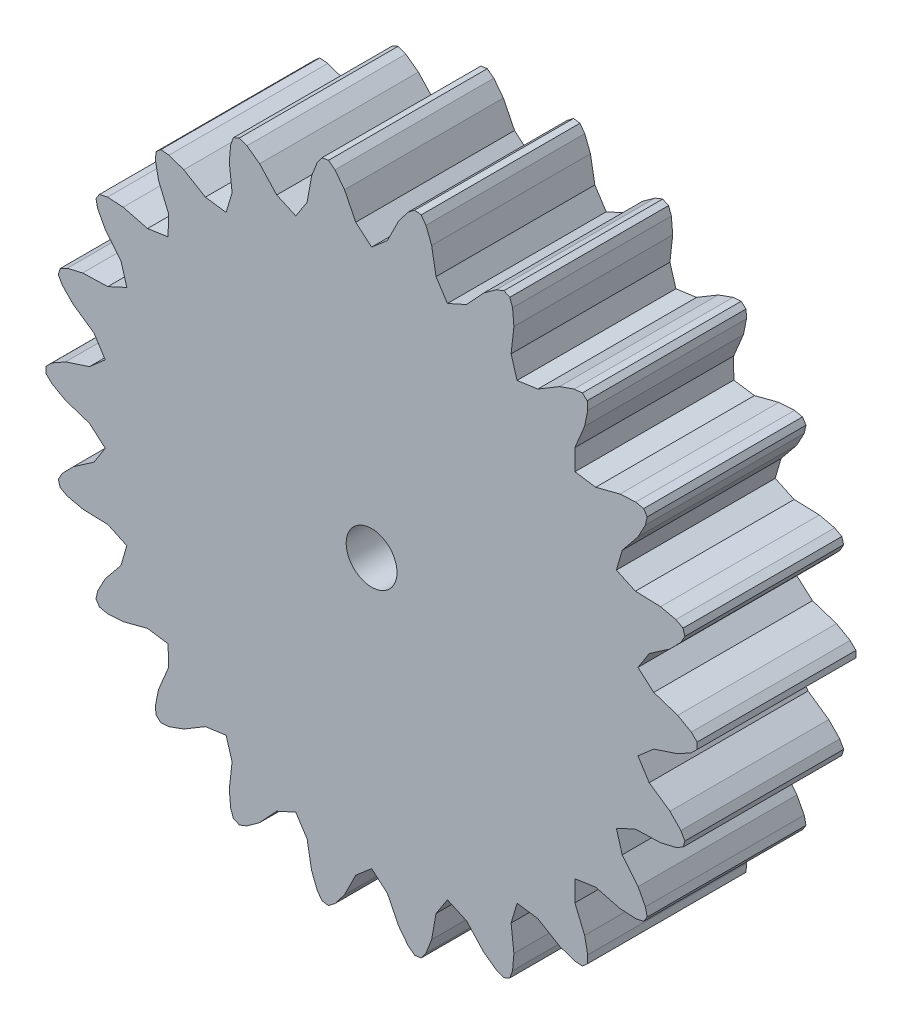
SolidWorks part; units mm, degrees
ref_plane "Front Plane" through (0, 0, 0) normal (0, 0, 1) x (1, 0, 0)
ref_plane "Top Plane" through (0, 0, 0) normal (0, 1, 0) x (1, 0, 0)
ref_plane "Right Plane" through (0, 0, 0) normal (1, 0, 0) x (0, 0, -1)
sketch "Sketch1" plane through (0, 0, 0) normal (0, 0, 1) x (1, 0, 0)
  line L1 (1.2374, -1.2374) -> (-1.2374, -1.2374) construction
  line L2 (1.2374, -1.2374) -> (1.2374, 1.2374) construction
  line L3 (1.2374, 1.2374) -> (-1.2374, 1.2374) construction
  line L4 (-1.2374, -1.2374) -> (-1.2374, 1.2374) construction
  line L5 (1.2374, -1.2374) -> (-1.2374, 1.2374) construction
  line L6 (1.2374, 1.2374) -> (-1.2374, -1.2374) construction
  circle A0 centre (0, 0) radius 20.5
  circle A1 centre (0, 0) radius 1.75 construction
  dimension "D1" = 41
  dimension "D2" = 3.5
extrude "Boss-Extrude1" add sketch "Sketch1" along normal blind 10
sketch "Sketch2" plane through (0, 0, 0) normal (0, 0, 1) x (1, 0, 0)
  line L0 (0, 0) -> (0, 10.088) construction
  line L1 (0, 16.9447) -> (-0.9985, 17.8041)
  line L8 (-2.7154, 20.3194) -> (0, 24.5037)
  line L11 (-0.9985, 17.8041) -> (-1.7043, 19.2252)
  line L12 (-1.7043, 19.2252) -> (-2.3066, 20.0063)
  line L13 (-2.3066, 20.0063) -> (-2.7154, 20.3194)
  line L14 (2.3066, 20.0063) -> (2.7154, 20.3194)
  line L15 (1.7043, 19.2252) -> (2.3066, 20.0063)
  line L16 (0.9985, 17.8041) -> (1.7043, 19.2252)
  line L17 (2.7154, 20.3194) -> (0, 24.5037)
  line L18 (0, 16.9447) -> (0.9985, 17.8041)
  circle A14 centre (0, 0) radius 20.5 construction
  point P16 (0, 20.5)
extrude "Cut-Extrude1" cut sketch "Sketch2" along normal through all
sketch "Sketch3" plane through (0, 0, 0) normal (0, 0, 1) x (1, 0, 0)
  circle A0 centre (0, 0) radius 7.5
  dimension "D1" = 15
sketch "Sketch4" plane through (0, 0, 10) normal (0, 0, 1) x (1, 0, 0)
  circle A0 centre (0, 0) radius 1.6
  dimension "D1" = 3.2
extrude "Cut-Extrude2" cut sketch "Sketch4" against normal through all both and the other way through all
pattern_circular "CirPattern1" count 22 over 360 about axis through (0, 0, 10) along (0, 0, -1) of "Cut-Extrude1" reverse direction yes
equation "\"circle\"=41"
equation "\"D1@Sketch1\"=\"circle\""
equation "\"separator_width\"=45"
equation "\"big-gear-thiccness\"=2"
equation "\"D1@Boss-Extrude1\"=10"
